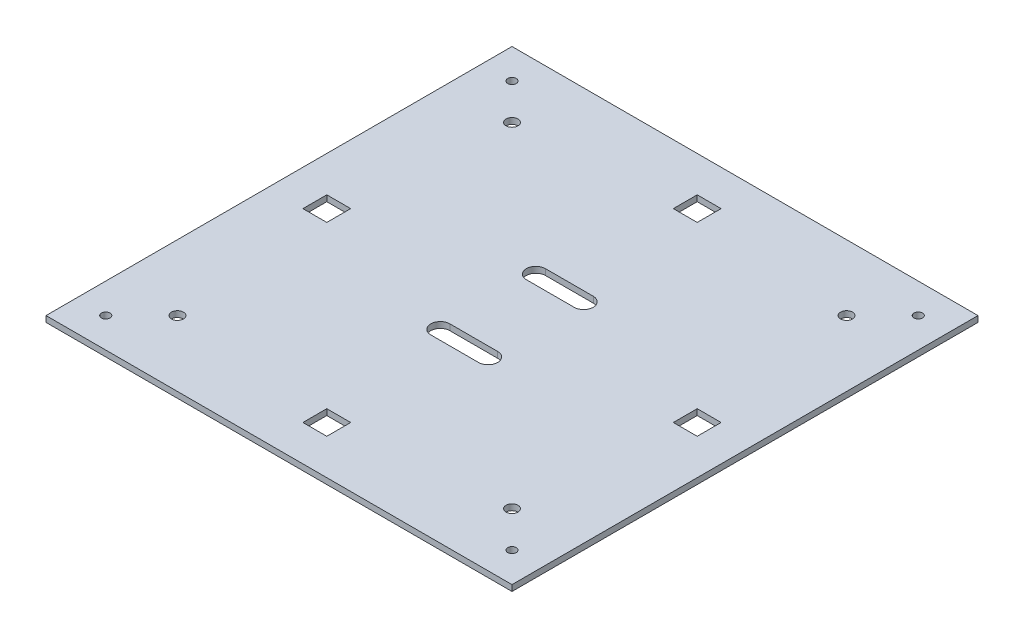
SolidWorks part; units mm, degrees
ref_plane "Front Plane" through (0, 0, 0) normal (0, 0, 1) x (1, 0, 0)
ref_plane "Top Plane" through (0, 0, 0) normal (0, 1, 0) x (1, 0, 0)
ref_plane "Right Plane" through (0, 0, 0) normal (1, 0, 0) x (0, 0, -1)
sketch "Sketch1" plane through (0, 0, 0) normal (0, 1, 0) x (1, 0, 0)
  line L1 (0, 0) -> (241.3, 0)
  line L2 (0, 0) -> (0, 241.3)
  line L3 (0, 241.3) -> (241.3, 241.3)
  line L4 (241.3, 0) -> (241.3, 241.3)
  dimension "9.5" = 241.3
  dimension "D2" = 241.3
extrude "Main Body" add sketch "Sketch1" along normal blind 3.175
sketch "Sketch2" plane through (0, 3.175, 0) normal (0, 1, 0) x (1, 0, 0)
  line L0 (0, 0) -> (241.3, 0) construction
  line L1 (241.3, 0) -> (241.3, 241.3) construction
  line L2 (0, 0) -> (241.3, 241.3) construction
  circle A8 centre (209.55, 31.75) radius 3.175
  circle A9 centre (31.75, 31.75) radius 3.175
  circle A10 centre (31.75, 209.55) radius 3.175
  circle A11 centre (209.55, 209.55) radius 3.175
  circle A16 centre (228.6, 12.7) radius 2.286
  circle A17 centre (12.7, 12.7) radius 2.286
  circle A18 centre (12.7, 228.6) radius 2.286
  circle A19 centre (228.6, 228.6) radius 2.286
  point P10 (120.65, 120.65)
  dimension "D2" = 12.7
  dimension "D9" = 6.35
  dimension "D10" = 31.75
  dimension "D11" = 31.75
  dimension "D4" = 4.572
  dimension "D12" = 125.7236
  dimension "D13" = 177.8
  dimension "D3" = 12.7
  dimension "D5" = 4
  dimension "D7" = 215.9
  dimension "D8" = 152.6644
  dimension "D6" = 4
extrude "Screw and String Holes" cut sketch "Sketch2" against normal through all
sketch "Sketch3" plane through (0, 3.175, 0) normal (0, 1, 0) x (1, 0, 0)
  line L0 (241.3, 0) -> (241.3, 241.3) construction
  line L1 (241.3, 241.3) -> (0, 241.3) construction
  line L2 (0, 241.3) -> (0, 0) construction
  line L3 (0, 0) -> (241.3, 0) construction
  line L4 (241.3, 0) -> (241.3, 241.3)
  line L5 (241.3, 241.3) -> (0, 241.3)
  line L6 (0, 241.3) -> (0, 0)
  line L7 (0, 0) -> (241.3, 0)
  line L8 (-3.175, 244.475) -> (-3.175, -3.175)
  line L9 (-3.175, -3.175) -> (244.475, -3.175)
  line L10 (244.475, -3.175) -> (244.475, 244.475)
  line L11 (244.475, 244.475) -> (-3.175, 244.475)
  dimension "D1" = 3.175
extrude "Slight Expansion" add sketch "Sketch3" against normal blind 3.175
sketch "Sketch4" plane through (0, 3.175, 0) normal (0, 1, 0) x (1, 0, 0)
  line L0 (-3.175, -3.175) -> (244.475, 244.475) construction
  line L1 (-3.175, -3.175) -> (244.475, -3.175) construction
  line L2 (114.3, 28.575) -> (127, 28.575)
  line L3 (114.3, 28.575) -> (114.3, 15.875)
  line L4 (114.3, 15.875) -> (127, 15.875)
  line L5 (127, 28.575) -> (127, 15.875)
  line L6 (15.875, 127) -> (15.875, 114.3)
  line L7 (28.575, 114.3) -> (15.875, 114.3)
  line L8 (28.575, 127) -> (15.875, 127)
  line L9 (28.575, 127) -> (28.575, 114.3)
  line L10 (127, 225.425) -> (114.3, 225.425)
  line L11 (114.3, 212.725) -> (114.3, 225.425)
  line L12 (127, 212.725) -> (127, 225.425)
  line L13 (127, 212.725) -> (114.3, 212.725)
  line L14 (225.425, 114.3) -> (225.425, 127)
  line L15 (212.725, 127) -> (225.425, 127)
  line L16 (212.725, 114.3) -> (225.425, 114.3)
  line L17 (212.725, 114.3) -> (212.725, 127)
  line L18 (-3.175, 244.475) -> (-3.175, -3.175) construction
  point P10 (120.65, 15.875)
  point P11 (120.65, -3.175)
  point P12 (120.65, 120.65)
  point P13 (15.875, 120.65)
  point P28 (-3.175, 120.65)
  dimension "D1" = 12.7
  dimension "D2" = 12.7
  dimension "D3" = 19.05
  dimension "D5" = 19.05
  dimension "D4" = 4
extrude "LED Holes" cut sketch "Sketch4" against normal through all
sketch "Sketch5" plane through (0, 3.175, 0) normal (0, 1, 0) x (1, 0, 0)
  line L0 (107.95, 95.25) -> (133.35, 95.25) construction
  line L1 (107.95, 100.33) -> (133.35, 100.33)
  line L2 (107.95, 90.17) -> (133.35, 90.17)
  line L3 (107.95, 146.05) -> (133.35, 146.05) construction
  line L4 (107.95, 151.13) -> (133.35, 151.13)
  line L5 (107.95, 140.97) -> (133.35, 140.97)
  line L6 (127, 28.575) -> (114.3, 28.575) construction
  line L7 (120.65, 146.05) -> (120.65, 95.25) construction
  line L8 (244.475, -3.175) -> (244.475, 244.475) construction
  arc A0 (107.95, 100.33) -> (107.95, 90.17) centre (107.95, 95.25) ccw
  arc A1 (133.35, 90.17) -> (133.35, 100.33) centre (133.35, 95.25) ccw
  arc A2 (107.95, 151.13) -> (107.95, 140.97) centre (107.95, 146.05) ccw
  arc A3 (133.35, 140.97) -> (133.35, 151.13) centre (133.35, 146.05) ccw
  point P2 (120.65, 95.25)
  point P9 (120.65, 146.05)
  point P17 (120.65, 28.575)
  point P19 (120.65, 120.65)
  point P22 (244.475, 120.65)
  dimension "D1" = 25.4
  dimension "D2" = 50.8
  dimension "D3" = 10.16
extrude "External Cable Slots" cut sketch "Sketch5" against normal through all
